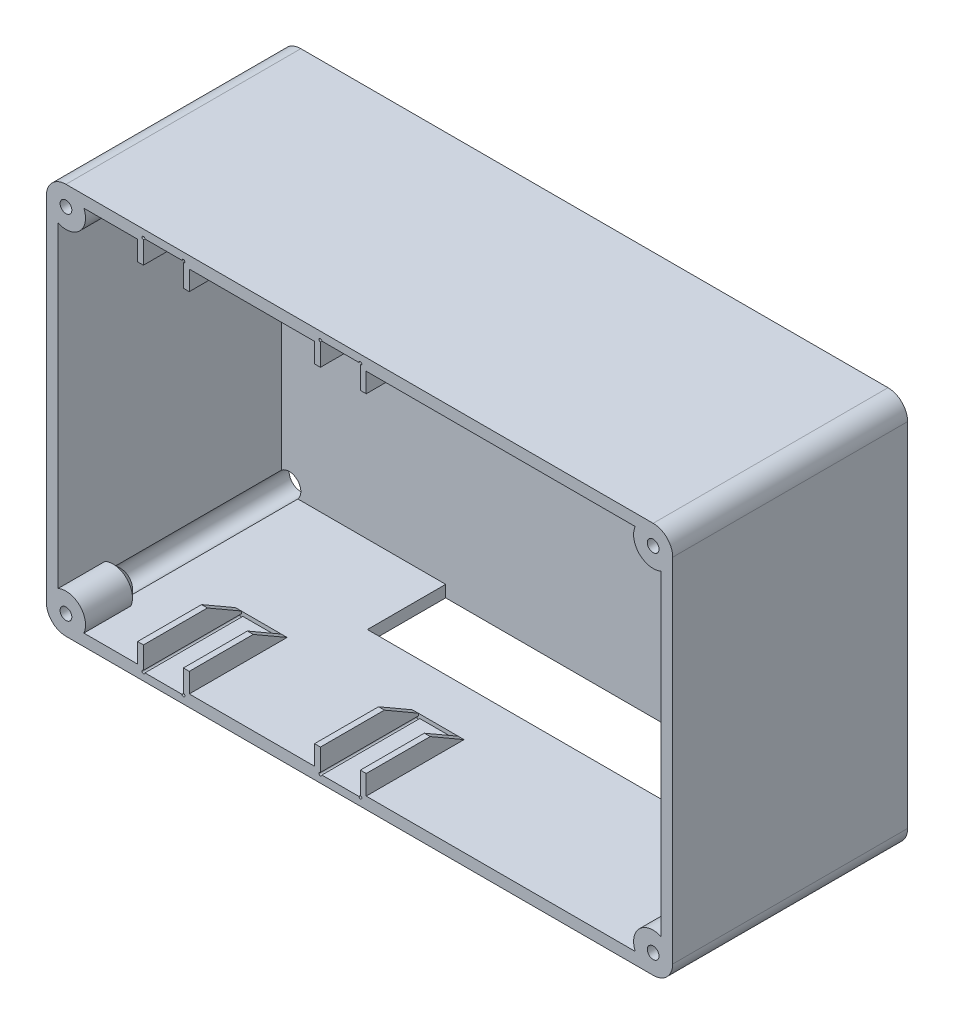
SolidWorks part; units mm, degrees
ref_plane "Front Plane" through (0, 0, 0) normal (0, 0, 1) x (1, 0, 0)
ref_plane "Top Plane" through (0, 0, 0) normal (0, 1, 0) x (1, 0, 0)
ref_plane "Right Plane" through (0, 0, 0) normal (1, 0, 0) x (0, 0, -1)
sketch "BaseShape" plane through (0, 0, 0) normal (0, 0, 1) x (1, 0, 0)
  line L1 (0, 0) -> (-160, 0)
  line L2 (0, 0) -> (0, -100)
  line L3 (0, -100) -> (-160, -100)
  line L4 (-160, 0) -> (-160, -100)
extrude "ContainerBase" add sketch "BaseShape" along normal blind 60
fillet "SideCornerFillet" radius 5 4 edges at (-160, 0, 30) (-160, -100, 30) (0, 0, 30) (0, -100, 30)
shell "ContainerShell" thickness 3 removed face at (-80, -50, 60)
sketch "SlotSketch" plane through (0, -3, 0) normal (0, -1, 0) x (1, 0, 0)
  line L0 (-155, 60) -> (-5, 60) construction
  line L1 (-135.2, 60) -> (-125, 60)
  line L2 (-135.2, 60) -> (-135.2, 35)
  line L3 (-135.2, 35) -> (-125, 35)
  line L4 (-125, 60) -> (-125, 35)
  line L5 (-5, 60) -> (-155, 60) construction
  line L6 (-90, 60) -> (-79.8, 60)
  line L7 (-160, 60) -> (-160, 0) construction
  line L8 (-90, 60) -> (-90, 35)
  line L9 (-90, 35) -> (-79.8, 35)
  line L10 (-79.8, 60) -> (-79.8, 35)
  dimension "D1" = 35
  dimension "D2" = 10.2
  dimension "D3" = 25
  dimension "D4" = 35
  dimension "D5" = 10.2
  dimension "D6" = 25
extrude "SlotCut" cut sketch "SlotSketch" against normal blind 1
ref_plane "SlotsMirroringPlane" through (0, -50, 0) normal (0, -1, 0) x (-1, 0, 0)
mirror "MirrorSlots" about plane through (0, -50, 0) normal (0, -1, 0) of "SlotCut"
sketch "ElectronicsViewHole" plane through (0, -100, 0) normal (0, -1, 0) x (1, 0, 0)
  line L1 (-15, 3) -> (-115, 3)
  line L2 (-15, 3) -> (-15, 23)
  line L3 (-15, 23) -> (-115, 23)
  line L4 (-115, 3) -> (-115, 23)
  line L5 (-155, 0) -> (-5, 0) construction
  line L6 (-5, 0) -> (-5, 60) construction
  dimension "D1" = 100
  dimension "D2" = 3
  dimension "D3" = 10
extrude "ViewElectronicsHole" cut sketch "ElectronicsViewHole" against normal up to next
sketch "ScrewSupports" plane through (0, 0, 60) normal (0, 0, 1) x (1, 0, 0)
  circle A0 centre (-155, -5) radius 5
  circle A1 centre (-155, -95) radius 5
  circle A2 centre (-5, -95) radius 5
  circle A3 centre (-5, -5) radius 5
extrude "Boss-Extrude3" add sketch "ScrewSupports" against normal blind 15
chamfer "ScrewSupportTaper" distance 3 angle 45 4 edges at (-151.4645, -8.5355, 45) (-8.5355, -91.4645, 45) (-8.5355, -8.5355, 45) (-151.4645, -91.4645, 45)
sketch "Sketch5" plane through (0, 0, 0) normal (0, 0, -1) x (-1, 0, 0)
  circle A0 centre (5, -5) radius 3
  circle A1 centre (5, -95) radius 3
  circle A2 centre (155, -95) radius 3
  circle A3 centre (155, -5) radius 3
  dimension "D1" = 6
  dimension "D2" = 6
  dimension "D3" = 6
  dimension "D4" = 6
extrude "CounterSinkCut" cut sketch "Sketch5" against normal blind 52
sketch "Sketch6" plane through (0, 0, 60) normal (0, 0, 1) x (1, 0, 0)
  line L4 (-5, 0) -> (-155, 0)
  line L5 (-160, -5) -> (-160, -95)
  line L6 (-155, -100) -> (-5, -100)
  line L7 (0, -95) -> (0, -5)
  line L8 (-5, 0) -> (-155, 0)
  line L9 (-160, -5) -> (-160, -95)
  line L10 (-155, -100) -> (-5, -100)
  line L11 (0, -95) -> (0, -5)
  circle A0 centre (-155, -5) radius 1.5
  circle A1 centre (-155, -95) radius 1.5
  circle A2 centre (-5, -95) radius 1.5
  circle A3 centre (-5, -5) radius 1.5
  arc A6 (0, -5) -> (-5, 0) centre (-5, -5) ccw
  arc A7 (-155, 0) -> (-160, -5) centre (-155, -5) ccw
  arc A8 (-160, -95) -> (-155, -100) centre (-155, -95) ccw
  arc A9 (-5, -100) -> (0, -95) centre (-5, -95) ccw
  arc A10 (0, -5) -> (-5, 0) centre (-5, -5) ccw
  arc A11 (-155, 0) -> (-160, -5) centre (-155, -5) ccw
  arc A12 (-160, -95) -> (-155, -100) centre (-155, -95) ccw
  arc A13 (-5, -100) -> (0, -95) centre (-5, -95) ccw
  dimension "D1" = 3
  dimension "D2" = 3
  dimension "D4" = 3
  dimension "D5" = 3
  dimension "D3" = 0
other "AlignGroup1"
extrude "ScrewHoles" cut sketch "Sketch6" against normal blind 52 contours A1 | A2 | A3 | A0
sketch "Sketch7" plane through (0, -3, 0) normal (0, -1, 0) x (1, 0, 0)
  line L1 (-135.2, 60) -> (-136.7, 60)
  line L2 (-135.2, 60) -> (-135.2, 35)
  line L3 (-135.2, 35) -> (-136.7, 35)
  line L4 (-136.7, 60) -> (-136.7, 35)
  line L5 (-125, 60) -> (-123.5, 60)
  line L6 (-125, 60) -> (-125, 35)
  line L7 (-125, 35) -> (-123.5, 35)
  line L8 (-123.5, 60) -> (-123.5, 35)
  line L9 (-90, 60) -> (-91.5, 60)
  line L10 (-90, 60) -> (-90, 35)
  line L11 (-90, 35) -> (-91.5, 35)
  line L12 (-91.5, 60) -> (-91.5, 35)
  line L13 (-79.8, 60) -> (-78.3, 60)
  line L14 (-79.8, 60) -> (-79.8, 35)
  line L15 (-79.8, 35) -> (-78.3, 35)
  line L16 (-78.3, 60) -> (-78.3, 35)
  dimension "D1" = 1.5
  dimension "D2" = 1.5
  dimension "D3" = 1.5
  dimension "D4" = 1.5
extrude "Boss-Extrude4" add sketch "Sketch7" along normal blind 5
ref_plane "Plane1" through (0, -50, 0) normal (0, 1, 0) x (1, 0, 0)
chamfer "Chamfer1" distance 5 angle 60 4 edges at (-135.95, -8, 35) (-124.25, -8, 35) (-79.05, -8, 35) (-90.75, -8, 35) first distance on face at (-135.95, -5.5, 35) first distance on face at (-124.25, -5.5, 35) first distance on face at (-79.05, -5.5, 35) first distance on face at (-90.75, -5.5, 35)
mirror "Mirror3" about plane through (0, -50, 0) normal (0, 1, 0) of "Chamfer1", "Boss-Extrude4"
sketch "Sketch8" plane through (0, 0, 60) normal (0, 0, 1) x (1, 0, 0)
  circle A0 centre (-135.2, -2) radius 0.375
  circle A1 centre (-125, -2) radius 0.375
  circle A2 centre (-90, -2) radius 0.375
  circle A3 centre (-79.8, -2) radius 0.375
  circle A4 centre (-135.2, -98) radius 0.375
  circle A5 centre (-90, -98) radius 0.375
  circle A6 centre (-125, -98) radius 0.375
  circle A7 centre (-79.8, -98) radius 0.375
  dimension "D1" = 0.75
extrude "Cut-Extrude1" cut sketch "Sketch8" against normal blind 25
